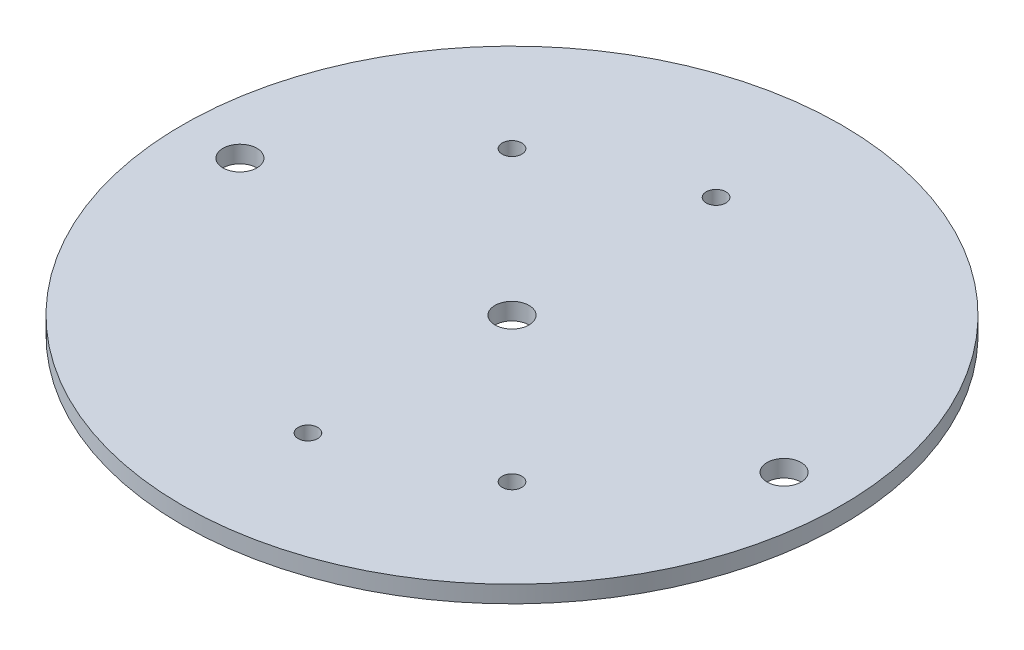
SolidWorks part; units mm, degrees
ref_plane "Front Plane" through (0, 0, 0) normal (0, 0, 1) x (1, 0, 0)
ref_plane "Top Plane" through (0, 0, 0) normal (0, 1, 0) x (1, 0, 0)
ref_plane "Right Plane" through (0, 0, 0) normal (1, 0, 0) x (0, 0, -1)
sketch "Sketch2" plane through (0, 0, 0) normal (0, 1, 0) x (1, 0, 0)
  line L0 (-50.8, 0) -> (50.8, 0) construction
  line L1 (0, -38.1) -> (0, 38.1) construction
  line L2 (-26.9408, 26.9408) -> (26.9408, -26.9408) construction
  circle A0 centre (0, 0) radius 61.5315
  circle A1 centre (-50.8, 0) radius 3.175
  circle A2 centre (50.8, 0) radius 3.175
  circle A3 centre (0, 0) radius 3.175
  circle A4 centre (0, 38.1) radius 1.8288
  circle A5 centre (0, -38.1) radius 1.8288
  circle A8 centre (-26.9408, 26.9408) radius 1.8288
  circle A9 centre (26.9408, -26.9408) radius 1.8288
  point P6 (0, 0)
  point P12 (0, 0)
  point P17 (0, 0)
  point P18 (0, 0)
  dimension "D1" = 123.063
  dimension "D3" = 6.35
  dimension "D4" = 6.35
  dimension "D5" = 3.6576
  dimension "D6" = 76.2
  dimension "D8" = 45
  dimension "D2" = 101.6
  dimension "D7" = 76.2
extrude "Boss-Extrude1" add sketch "Sketch2" along normal blind 3.175
